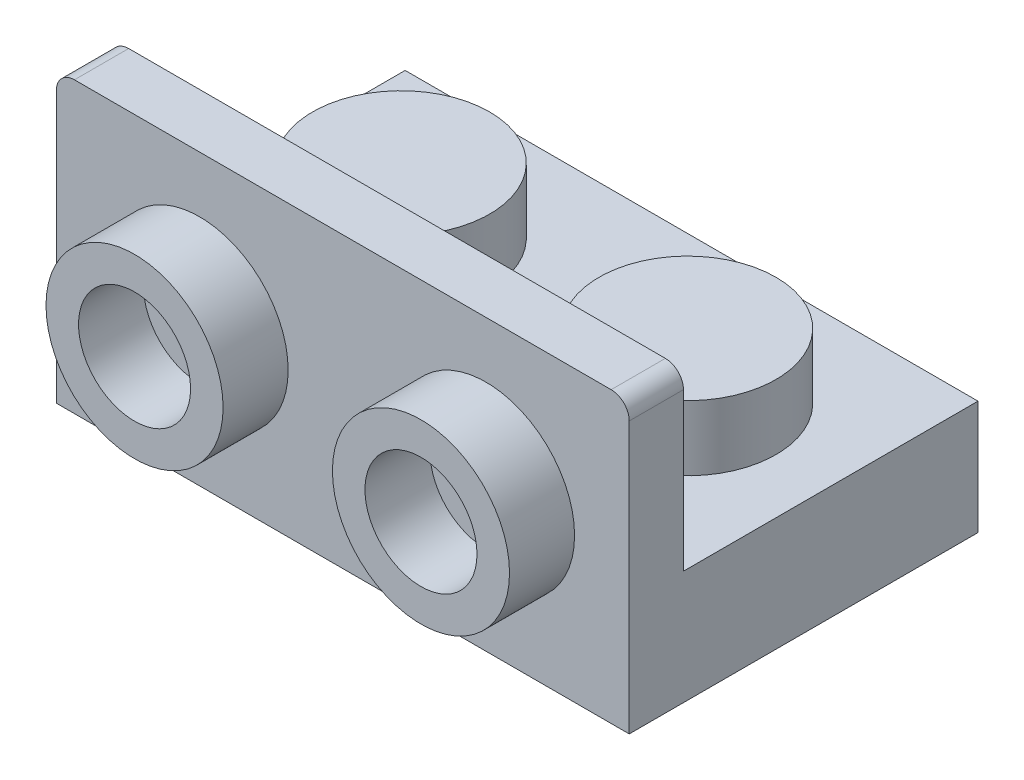
SolidWorks part; units mm, degrees
ref_plane "Front Plane" through (0, 0, 0) normal (0, 0, 1) x (1, 0, 0)
ref_plane "Top Plane" through (0, 0, 0) normal (0, 1, 0) x (1, 0, 0)
ref_plane "Right Plane" through (0, 0, 0) normal (1, 0, 0) x (0, 0, -1)
sketch "Sketch1" plane through (0, 0, 0) normal (1, 0, 0) x (0, 0, -1)
  line L0 (0, 0) -> (0, 8)
  line L1 (0, 8) -> (1.5, 8)
  line L2 (1.5, 8) -> (1.5, 3.15)
  line L3 (1.5, 3.15) -> (9.65, 3.15)
  line L4 (9.65, 3.15) -> (9.65, 0)
  line L5 (9.65, 0) -> (0, 0)
  dimension "D1" = 1.5
  dimension "D2" = 3.15
  dimension "D3" = 9.65
  dimension "D4" = 4.85
extrude "Boss-Extrude1" add sketch "Sketch1" against normal blind 15.85
sketch "Sketch2" plane through (0, 0, 0) normal (0, 0, 1) x (1, 0, 0)
  line L1 (-15.85, 8) -> (-15.85, 0) construction
  line L2 (0, 8) -> (0, 0) construction
  line L3 (-15.85, 8) -> (0, 8) construction
  circle A0 centre (-11.8875, 4) radius 2.45
  circle A1 centre (-11.8875, 4) radius 1.55
  circle A2 centre (-3.9625, 4) radius 2.45
  circle A3 centre (-3.9625, 4) radius 1.55
  dimension "D2" = 3.9625
  dimension "D5" = 4.9
  dimension "D6" = 4.9
  dimension "D7" = 3.1
  dimension "D8" = 3.1
  dimension "D1" = 3.9625
  dimension "D3" = 4
  dimension "D4" = 4
extrude "Boss-Extrude2" add sketch "Sketch2" along normal blind 1.8
sketch "Sketch3" plane through (0, 3.15, 0) normal (0, 1, 0) x (1, 0, 0)
  line L0 (-15.85, 9.65) -> (0, 9.65) construction
  line L2 (-15.85, 9.65) -> (-15.85, 1.5) construction
  line L3 (0, 9.65) -> (0, 1.5) construction
  circle A0 centre (-11.8875, 5.575) radius 2.45
  circle A1 centre (-3.9625, 5.575) radius 2.45
  dimension "D4" = 3.9625
  dimension "D5" = 4.9
  dimension "D6" = 4.9
  dimension "D1" = 4.075
  dimension "D2" = 4.075
  dimension "D3" = 3.9625
extrude "Boss-Extrude3" add sketch "Sketch3" along normal blind 1.8
shell "Shell1" thickness 1.5 removed face at (-7.925, 0, -4.825)
fillet "Fillet1" radius 0.5 2 edges at (-15.85, 8, -0.75) (0, 8, -0.75)
